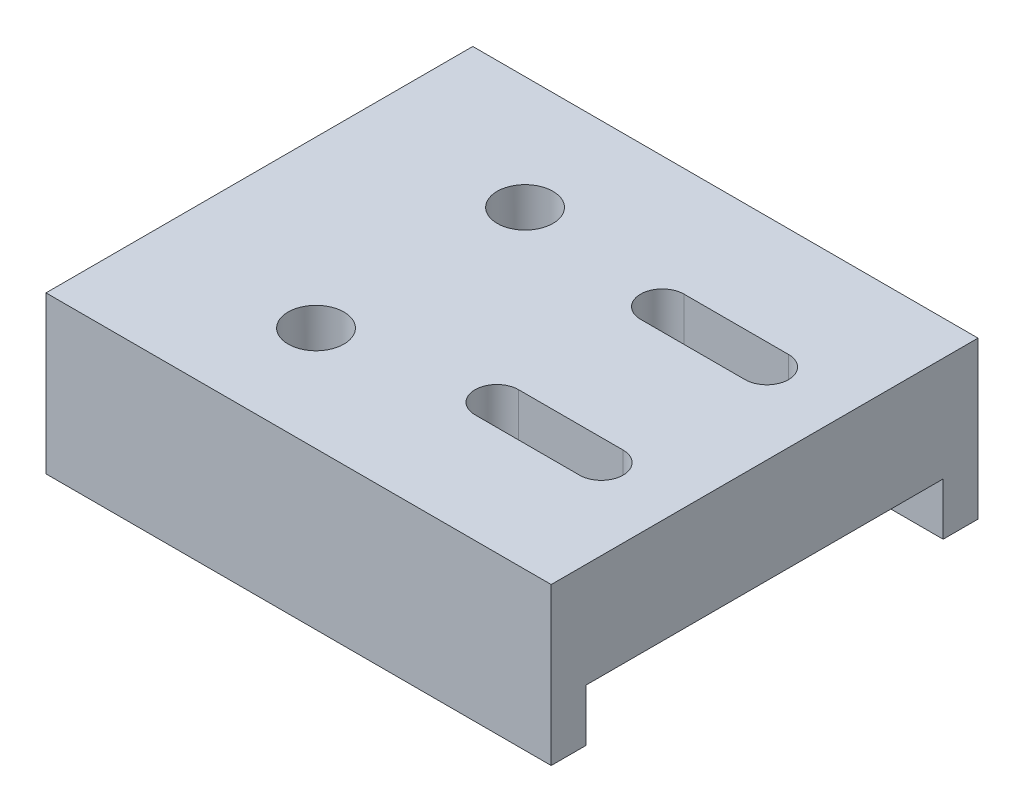
SolidWorks part; units mm, degrees
material "ABS"
ref_plane "Front" through (0, 0, 0) normal (0, 0, 1) x (1, 0, 0)
ref_plane "Top" through (0, 0, 0) normal (0, 1, 0) x (1, 0, 0)
ref_plane "Right" through (0, 0, 0) normal (1, 0, 0) x (0, 0, -1)
sketch "Esquisse1" plane through (0, 0, 0) normal (1, 0, 0) x (0, 0, -1)
  line L0 (24.5, 0) -> (0, 0)
  line L1 (0, 0) -> (0, -14)
  dimension "D1" = 90
  dimension "D2" = 24.5
  dimension "D3" = 14
extrude "Extru.-Mince1" add sketch "Esquisse1" along normal mid plane 19 thin thin type one direction reverse wall 6
fillet "Congé2" [suppressed] radius 2
sketch "Esquisse2" plane through (0, 0, 0) normal (0, 1, 0) x (1, 0, 0)
  line L1 (9.5, 0) -> (-9.5, 0) construction
  circle A1 centre (0, 18) radius 1.6
  dimension "D2" = 18
  dimension "D3" = 3.2
extrude "Enlèv. mat.-Extru.1" cut sketch "Esquisse2" against normal through all
sketch "Esquisse3" plane through (0, 0, 0) normal (0, 0, 1) x (1, 0, 0)
  line L0 (9.5, -14) -> (-9.5, -14) construction
  line L2 (9.5, 0) -> (-9.5, 0) construction
  circle A0 centre (0, -9) radius 1.6
  dimension "D1" = 5
  dimension "D2" = 3.2
  dimension "D3" = 9
extrude "Enlèv. mat.-Extru.2" [suppressed] cut sketch "Esquisse3" against normal through all
sketch "Esquisse4" plane through (0, 0, 0) normal (0, 1, 0) x (1, 0, 0)
  circle A0 centre (0, 18) radius 3.1
  circle A1 centre (0, 18) radius 1.6 construction
  dimension "D1" = 6.2
extrude "Enlèv. mat.-Extru.3" cut sketch "Esquisse4" against normal through all from offset 2.5 offset against normal yes
sketch "Esquisse5" [suppressed] plane through (0, 0, 0) normal (0, 0, 1) x (1, 0, 0)
  line L13 (-1.5877, -6.25) -> (-3.1754, -9)
  line L14 (-3.1754, -9) -> (-1.5877, -11.75)
  line L15 (-1.5877, -11.75) -> (1.5877, -11.75)
  line L16 (1.5877, -11.75) -> (3.1754, -9)
  line L17 (3.1754, -9) -> (1.5877, -6.25)
  line L18 (1.5877, -6.25) -> (-1.5877, -6.25)
  circle A3 centre (0, -9) radius 2.75 construction
  dimension "D1" = 5.5
extrude "Enlèv. mat.-Extru.4" [suppressed] cut sketch "Esquisse5" against normal blind 8 from offset 3 offset against normal yes
fillet "Congé1" [suppressed] radius 5
sketch "Esquisse6" plane through (0, 0, 0) normal (0, 1, 0) x (1, 0, 0)
  line L0 (9.5, 24.5) -> (-9.5, 24.5) construction
  line L1 (-2.35, 24.5) -> (2.35, 24.5)
  line L2 (-2.35, 24.5) -> (-2.35, 0)
  line L3 (-2.35, 0) -> (2.35, 0)
  line L4 (2.35, 24.5) -> (2.35, 0)
  circle A0 centre (0, 18) radius 1.6 construction
  circle A1 centre (0, 18) radius 1.6
  dimension "D1" = 4.7
extrude "Boss.-Extru.1" [suppressed] add sketch "Esquisse6" along normal blind 1.5
fillet "Congé3" [suppressed] radius 0.5
sketch "Esquisse7" [suppressed] plane through (0, 0, 0) normal (0, 0, 1) x (1, 0, 0)
  circle A1 centre (0, -9) radius 1.6 construction
  circle A2 centre (0, -9) radius 1.6
extrude "Boss.-Extru.2" [suppressed] add sketch "Esquisse7" against normal blind 0.2
sketch "Sketch1" [suppressed] plane through (0, 0, -15) normal (0, 0, -1) x (-1, 0, 0)
  line L1 (-2.35, 0) -> (3.0183, 0)
  line L2 (-2.35, 0) -> (-2.35, 3.1233)
  line L3 (-2.35, 3.1233) -> (3.0183, 3.1233)
  line L4 (3.0183, 0) -> (3.0183, 3.1233)
extrude "Cut-Extrude1" [suppressed] cut sketch "Sketch1" against normal through all
sketch "Sketch2" plane through (0, 0, -6) normal (0, 0, -1) x (-1, 0, 0)
  line L1 (-9.5, -6) -> (9.5, -6)
  line L2 (-9.5, -6) -> (-9.5, -14)
  line L3 (-9.5, -14) -> (9.5, -14)
  line L4 (9.5, -6) -> (9.5, -14)
extrude "Cut-Extrude2" cut sketch "Sketch2" against normal through all
sketch "Sketch4" plane through (0, -6, 0) normal (0, -1, 0) x (1, 0, 0)
  line L0 (9.5, -24.5) -> (9.5, 0) construction
  line L1 (-9.5, 0) -> (9.5, 0)
  line L2 (-9.5, 0) -> (-9.5, -2)
  line L3 (-9.5, -2) -> (9.5, -2)
  line L4 (9.5, 0) -> (9.5, -2)
  line L6 (-9.5, -24.5) -> (9.5, -24.5)
  line L7 (-9.5, -24.5) -> (-9.5, -22.5)
  line L8 (-9.5, -22.5) -> (9.5, -22.5)
  line L9 (9.5, -24.5) -> (9.5, -22.5)
  dimension "D1" = 2
extrude "Boss-Extrude2" add sketch "Sketch4" along normal blind 3
sketch "Sketch5" plane through (9.5, 0, 0) normal (1, 0, 0) x (0, 0, -1)
  line L8 (0, 0) -> (0, -9)
  line L9 (0, -9) -> (2, -9)
  line L10 (2, -9) -> (2, -6)
  line L11 (2, -6) -> (22.5, -6)
  line L12 (22.5, -6) -> (22.5, -9)
  line L13 (22.5, -9) -> (24.5, -9)
  line L14 (24.5, -9) -> (24.5, 0)
  line L15 (24.5, 0) -> (0, 0)
  line L16 (0, 0) -> (0, -9)
  line L17 (0, -9) -> (2, -9)
  line L18 (2, -9) -> (2, -6)
  line L19 (2, -6) -> (22.5, -6)
  line L20 (22.5, -6) -> (22.5, -9)
  line L21 (22.5, -9) -> (24.5, -9)
  line L22 (24.5, -9) -> (24.5, 0)
  line L23 (24.5, 0) -> (0, 0)
  dimension "D1" = 0
extrude "Boss-Extrude3" add sketch "Sketch5" along normal blind 10
sketch "Sketch6" plane through (0, -6, 0) normal (0, -1, 0) x (1, 0, 0)
  circle A0 centre (11.05, -8.4) radius 1.5
  dimension "D1" = 3
extrude "Cut-Extrude3" [suppressed] cut sketch "Sketch6" against normal through all
sketch "Sketch7" [suppressed] plane through (0, -6, 0) normal (0, -1, 0) x (1, 0, 0)
  line L0 (11.05, -6.15) -> (15.4501, -6.15) construction
  line L1 (11.05, -4.65) -> (15.4501, -4.65)
  line L2 (11.05, -7.65) -> (15.4501, -7.65)
  circle A0 centre (11.05, -6.15) radius 1.5 construction
  arc A1 (11.05, -7.65) -> (11.05, -4.65) centre (11.05, -6.15) ccw
  arc A3 (15.4501, -7.65) -> (15.4501, -4.65) centre (15.4501, -6.15) ccw
  point P3 (14.275, -6.15)
extrude "Cut-Extrude6" [suppressed] cut sketch "Sketch7" against normal through all
pattern_linear "LPattern1" count 2 spacing 12 along (0, 0, 1) of "Enlèv. mat.-Extru.1", "Enlèv. mat.-Extru.3"
sketch "Sketch8" plane through (0, -6, 0) normal (0, -1, 0) x (1, 0, 0)
  circle A0 centre (14.877, -17) radius 1.25
  circle A1 centre (14.877, -7.5) radius 1.25
extrude "Cut-Extrude7" cut sketch "Sketch8" against normal through all
sketch "Sketch9" plane through (0, -6, 0) normal (0, -1, 0) x (1, 0, 0)
  line L0 (14.877, -7.5) -> (8.877, -7.5) construction
  line L1 (14.877, -8.75) -> (8.877, -8.75)
  line L2 (14.877, -6.25) -> (8.877, -6.25)
  line L3 (14.877, -17) -> (8.877, -17) construction
  line L4 (14.877, -18.25) -> (8.877, -18.25)
  line L5 (14.877, -15.75) -> (8.877, -15.75)
  arc A0 (14.877, -8.75) -> (14.877, -6.25) centre (14.877, -7.5) ccw
  arc A1 (8.877, -6.25) -> (8.877, -8.75) centre (8.877, -7.5) ccw
  circle A2 centre (14.877, -7.5) radius 1.25 construction
  arc A3 (14.877, -18.25) -> (14.877, -15.75) centre (14.877, -17) ccw
  arc A4 (8.877, -15.75) -> (8.877, -18.25) centre (8.877, -17) ccw
  circle A5 centre (14.877, -17) radius 1.25 construction
  point P3 (11.877, -7.5)
  point P13 (11.877, -17)
  dimension "D1" = 6
extrude "Cut-Extrude8" cut sketch "Sketch9" against normal through all
